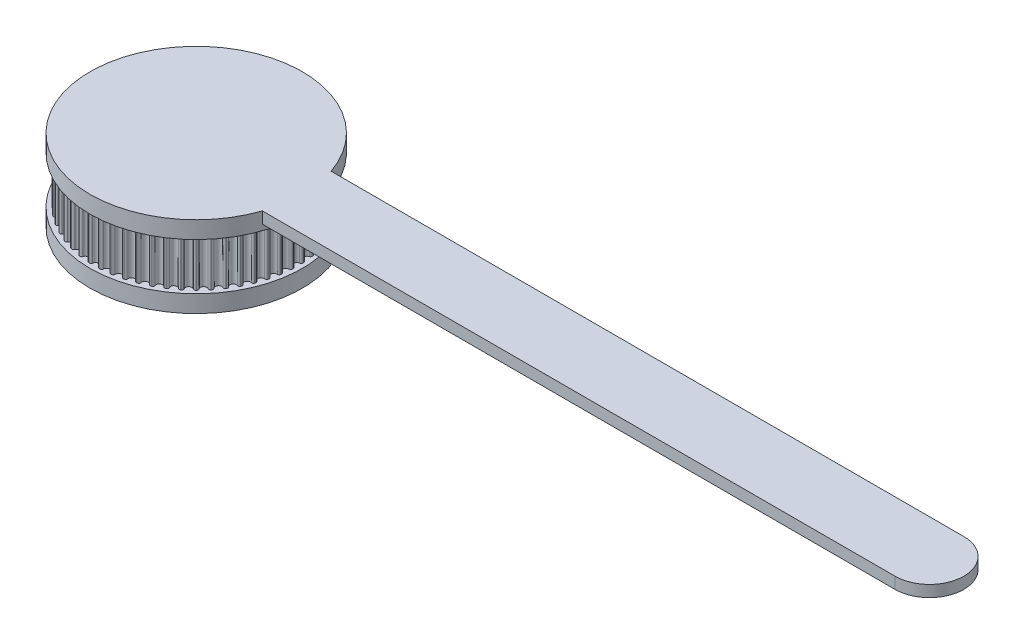
SolidWorks part; units mm, degrees
ref_plane "Front Plane" through (0, 0, 0) normal (0, 0, 1) x (1, 0, 0)
ref_plane "Top Plane" through (0, 0, 0) normal (0, 1, 0) x (1, 0, 0)
ref_plane "Right Plane" through (0, 0, 0) normal (1, 0, 0) x (0, 0, -1)
sketch "Sketch1" plane through (0, 0, 0) normal (0, 1, 0) x (1, 0, 0)
  line L0 (0, 0) -> (0, 28.2667) construction
  line L1 (0, 0) -> (2.9202, 27.7837) construction
  circle A0 centre (0, 0) radius 28.2667 construction
  circle A1 centre (0, 0) radius 27.0467 construction
  circle A2 centre (0, 27.9367) radius 0.89 construction
  circle A5 centre (2.9202, 27.7837) radius 0.89 construction
  arc A6 (0, 27.0467) -> (0.8804, 27.8061) centre (0, 27.9367) ccw
  arc A7 (0.8804, 27.8061) -> (1.3997, 28.2321) centre (1.3749, 27.7327) cw
  arc A8 (1.559, 28.2237) -> (2.031, 27.7458) centre (1.5314, 27.7245) cw
  arc A9 (2.8272, 26.8986) -> (2.031, 27.7458) centre (2.9202, 27.7837) cw
  arc A10 (1.3997, 28.2321) -> (1.559, 28.2237) centre (0, 0) cw
  arc A11 (0, 27.0467) -> (2.8272, 26.8986) centre (0, 0) ccw
  dimension "D1" = 56.5335
  dimension "D3" = 1.78
  dimension "D4" = 0.5
  dimension "D2" = 1.22
  dimension "D5" = 6
extrude "Boss-Extrude1" add sketch "Sketch1" along normal mid plane 13 contours A6 A11 A9 A8 A7 region at (0.001, 0, -0.0192)
ref_axis "Axis1" through (0, 3.3, 0) along (0, -1, 0)
pattern_circular "CirPattern1" count 60 over 360 about axis through (0, 3.3, 0) along (0, -1, 0) of "Boss-Extrude1"
sketch "Sketch2" plane through (0, 0, 0) normal (1, 0, 0) x (0, 0, -1)
  line L10 (0, 6.5) -> (29.4415, 6.5) construction
  line L11 (0, 6.5) -> (0, 8.0875) construction
  line L12 (0, 8.0875) -> (29.4415, 8.0875) construction
  line L15 (29.4415, 6.5) -> (29.4415, 8.0875) construction
  line L20 (0, 3.3) -> (0, -3.3) construction
  line L22 (29.4415, 8.0875) -> (0, 8.0875)
  line L23 (29.4415, 8.0875) -> (29.4415, 6.5)
  line L24 (29.4415, 6.5) -> (0, 6.5)
  line L25 (0, 8.0875) -> (0, 6.5)
  dimension "D1" = 1.5875
  dimension "D2" = 29.4415
  dimension "D3" = 6.5
revolve "Revolve3" add sketch "Sketch2" angle 360 about axis through (0, 3.3, 0) along (0, -1, 0) region at (0, 7.2937, -14.7207)
mirror "Mirror1" about plane through (0, 0, 0) normal (0, 1, 0) of "Revolve3"
sketch "Sketch7" plane through (0, 8.0875, 0) normal (0, 1, 0) x (1, 0, 0)
  line L0 (0, 0) -> (203.2, 0) construction
  line L1 (27.8581, 9.525) -> (203.2, 9.525)
  line L2 (27.8581, -9.525) -> (203.2, -9.525)
  arc A1 (203.2, -9.525) -> (203.2, 9.525) centre (203.2, 0) ccw
  arc A2 (27.8581, 9.525) -> (27.8581, -9.525) centre (0, 0) ccw
  circle A3 centre (0, 0) radius 29.4415 construction
  point P3 (101.6, 0)
  point P6 (27.8698, -9.525)
  point P9 (27.8572, -9.5222)
  point P13 (27.8374, -9.525)
  dimension "D1" = 203.2
  dimension "D2" = 19.05
extrude "Boss-Extrude4" add sketch "Sketch7" along normal blind 3.175
sketch "Sketch8" plane through (0, -8.0875, 0) normal (0, -1, 0) x (1, 0, 0)
  circle A0 centre (0, 0) radius 29.4415
  circle A1 centre (0, 0) radius 29.4415 construction
extrude "Boss-Extrude5" add sketch "Sketch8" along normal blind 3.175
equation "\"TEETH_NUM\"= 60"
equation "\"TOOTH_PITCH\"= 3mm"
equation "\"PITCH_LINE_OFFSET\"= .015in"
equation "\"DIAMETER_PER_GROOVE\"= \"OUTSIDE_DIAMETER\" / \"TEETH_NUM\" * 1in"
equation "\"PITCH_DIAMETER\"= ( ( \"TEETH_NUM\" * 3 - 1.31 ) / 3.1415 + .415 ) * 1mm"
equation "\"OUTSIDE_DIAMETER\"= \"PITCH_DIAMETER\" - \"PITCH_LINE_OFFSET\" * 2"
equation "\"D1@Sketch1\"=\"OUTSIDE_DIAMETER\""
equation "\"TOOTH_HEIGHT\"= 1.22mm"
equation "\"D2@Sketch1\"=\"TOOTH_HEIGHT\""
equation "\"TOOTH_DIAMETER\"= 1.78mm"
equation "\"INTERNAL_RADIUS\"= .5mm"
equation "\"D3@Sketch1\"=\"TOOTH_DIAMETER\""
equation "\"D5@Sketch1\"=360 / \"TEETH_NUM\""
equation "\"D4@Sketch1\"=\"INTERNAL_RADIUS\""
equation "\"D1@CirPattern1\"=\"TEETH_NUM\""
equation "\"BELT_GAP\"= 13mm"
equation "\"D2@Sketch2\"=\"PITCH_DIAMETER\"/2+1/32"
equation "\"D3@Sketch2\"=\"BELT_GAP\"/2"
equation "\"D1@Boss-Extrude1\"=\"BELT_GAP\""
